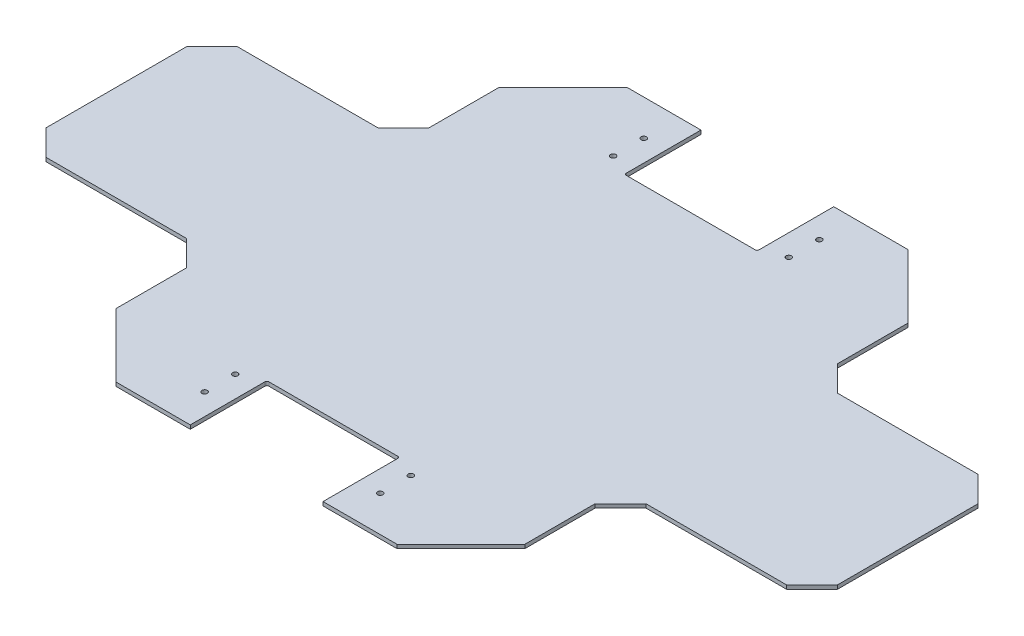
SolidWorks part; units mm, degrees
ref_plane "前视基准面" through (0, 0, 0) normal (0, 0, 1) x (1, 0, 0)
ref_plane "上视基准面" through (0, 0, 0) normal (0, 1, 0) x (1, 0, 0)
ref_plane "右视基准面" through (0, 0, 0) normal (1, 0, 0) x (0, 0, -1)
sketch "草图1" plane through (0, 0, 0) normal (0, 1, 0) x (1, 0, 0)
  line L0 (0, 0) -> (160, -38.7097) construction
  line L1 (-260, 200) -> (260, 200) construction
  line L2 (-260, 200) -> (-260, -200) construction
  line L3 (-260, -200) -> (260, -200) construction
  line L4 (260, 200) -> (260, -200) construction
  line L5 (-260, 200) -> (-160, 123.0769) construction
  line L6 (-260, -200) -> (-160, -123.0769) construction
  line L7 (-310, -75) -> (-160, -75)
  line L8 (-310, -75) -> (-310, 75)
  line L9 (-310, 75) -> (-160, 75)
  line L10 (310, -75) -> (310, 75)
  line L11 (-310, -75) -> (160, 38.7097) construction
  line L12 (-310, 75) -> (-160, 38.7097) construction
  line L13 (-160, -200) -> (160, -200)
  line L14 (-160, -200) -> (-160, -75)
  line L15 (-160, 200) -> (160, 200)
  line L16 (160, -200) -> (160, -75)
  line L17 (-60, -75) -> (0, 0) construction
  line L18 (0, 0) -> (60, -75) construction
  line L19 (-160, 75) -> (-160, 200)
  line L22 (160, 75) -> (310, 75)
  line L24 (97.5, 75) -> (260, 200) construction
  line L25 (160, 75) -> (160, 200)
  line L26 (260, 62.9032) -> (310, 75) construction
  line L27 (260, -62.9032) -> (310, -75) construction
  line L28 (160, -75) -> (310, -75)
  line L29 (160, -123.0769) -> (260, -200) construction
  point P0 (0, 0)
  point P6 (0, 0)
  point P11 (0, 0)
  dimension "D1" = 520
  dimension "D2" = 400
  dimension "D3" = 50
  dimension "D4" = 125
  dimension "D5" = 100
extrude "凸台-拉伸1" add sketch "草图1" along normal blind 3
chamfer "倒角1" distance 20 angle 45 8 edges at (-160, 1.5, -75) (-310, 1.5, -75) (-310, 1.5, 75) (-160, 1.5, 75) (160, 1.5, 75) (160, 1.5, -75) (310, 1.5, 75) (310, 1.5, -75)
chamfer "倒角2" distance 50 angle 45 4 edges at (160, 1.5, 200) (-160, 1.5, 200) (160, 1.5, -200) (-160, 1.5, -200)
sketch "草图2" plane through (0, 0, 0) normal (0, -1, 0) x (-1, 0, 0)
  line L1 (52, -140) -> (-52, -140)
  line L2 (52, -140) -> (52, -233.0888)
  line L3 (52, -233.0888) -> (-52, -233.0888)
  line L4 (-52, -140) -> (-52, -233.0888)
  line L6 (0, 0) -> (119.8246, 0) construction
  line L7 (-52, 140) -> (-52, 233.0888)
  line L8 (52, 233.0888) -> (-52, 233.0888)
  line L9 (52, 140) -> (52, 233.0888)
  line L10 (52, 140) -> (-52, 140)
  line L11 (160, -95) -> (160, -150) construction
  line L12 (-160, -150) -> (-160, -95) construction
  dimension "D1" = 108
  dimension "D2" = 108
extrude "切除-拉伸1" cut sketch "草图2" against normal blind 40
fillet "圆角1" radius 1.5 4 edges at (-52, 1.5, -140) (52, 1.5, -140) (52, 1.5, 140) (-52, 1.5, 140)
sketch "草图3" plane through (0, 0, 0) normal (0, -1, 0) x (1, 0, 0)
  circle A0 centre (-68.75, 172) radius 2.1
  circle A1 centre (-68.75, 148) radius 2.1
  circle A2 centre (68.75, 172) radius 2.1
  circle A3 centre (68.75, 148) radius 2.1
  circle A4 centre (-68.75, -148) radius 2.1
  circle A5 centre (-68.75, -172) radius 2.1
  circle A6 centre (68.75, -148) radius 2.1
  circle A7 centre (68.75, -172) radius 2.1
extrude "切除-拉伸2" cut sketch "草图3" against normal blind 80
